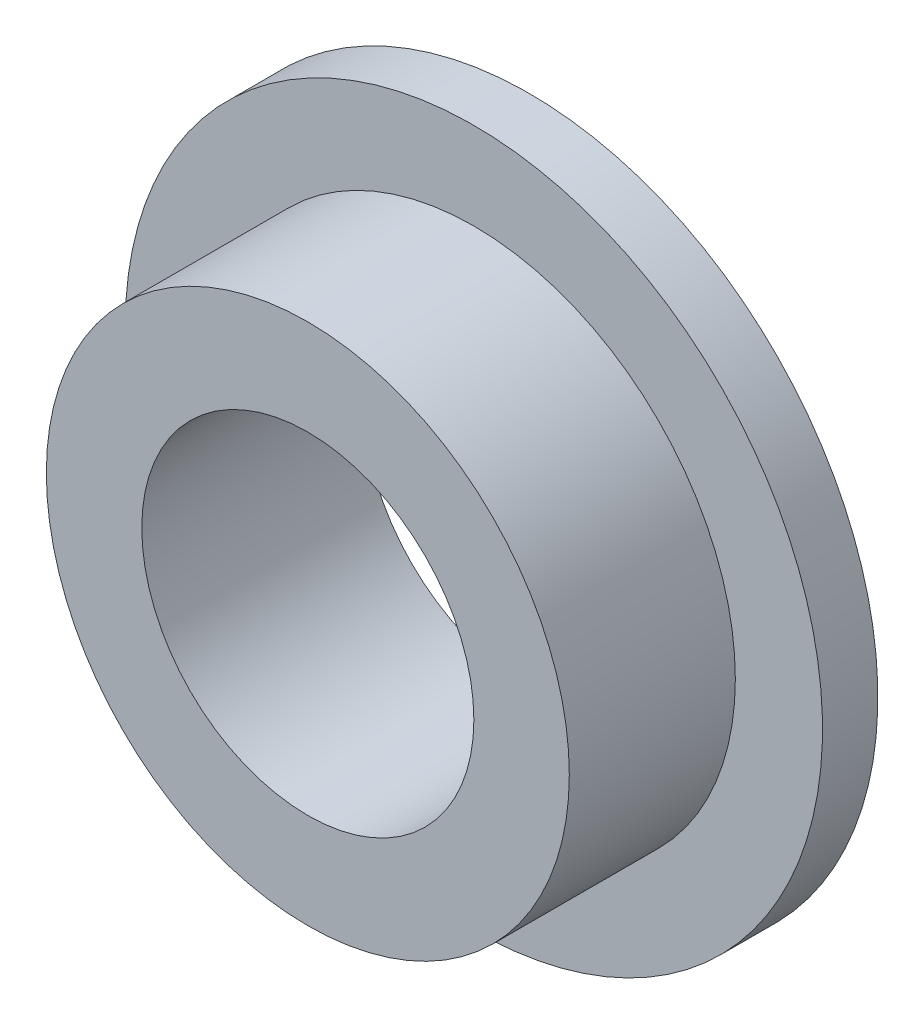
SolidWorks part; units mm, degrees
material "6061-T6 (SS)"
ref_plane "Front Plane" through (0, 0, 0) normal (0, 0, 1) x (1, 0, 0)
ref_plane "Top Plane" through (0, 0, 0) normal (0, 1, 0) x (1, 0, 0)
ref_plane "Right Plane" through (0, 0, 0) normal (1, 0, 0) x (0, 0, -1)
sketch "Sketch1" plane through (0, 0, 0) normal (0, 0, 1) x (1, 0, 0)
  circle A0 centre (0, 0) radius 15
  dimension "D1" = 30
extrude "Boss-Extrude1" add sketch "Sketch1" along normal blind 9.525
sketch "Sketch2" plane through (0, 0, 0) normal (0, 0, -1) x (-1, 0, 0)
  circle A0 centre (0, 0) radius 20
  dimension "D1" = 40
extrude "Boss-Extrude2" add sketch "Sketch2" along normal blind 3.175
sketch "Sketch3" plane through (0, 0, -3.175) normal (0, 0, -1) x (-1, 0, 0)
  circle A0 centre (0, 0) radius 9.525
  dimension "D1" = 19.05
extrude "Cut-Extrude1" cut sketch "Sketch3" against normal through all
equation "\"D1@Boss-Extrude2\"=0.125in"
equation "\"D1@Sketch3\"=0.75in"
